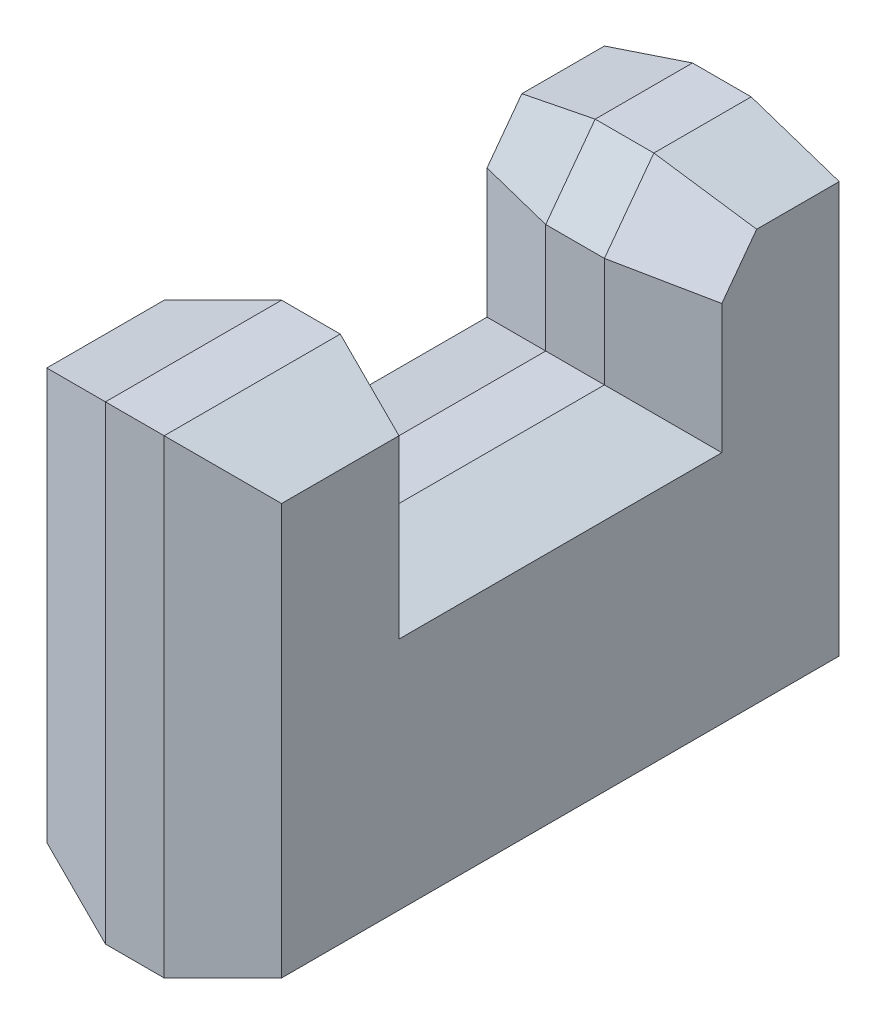
SolidWorks part; units mm, degrees
ref_plane "Front Plane" through (0, 0, 0) normal (0, 0, 1) x (1, 0, 0)
ref_plane "Top Plane" through (0, 0, 0) normal (0, 1, 0) x (1, 0, 0)
ref_plane "Right Plane" through (0, 0, 0) normal (1, 0, 0) x (0, 0, -1)
sketch "Sketch1" plane through (0, 0, 0) normal (0, 0, 1) x (1, 0, 0)
  line L0 (0, 4) -> (0, -4) construction
  line L1 (-2, 4) -> (2, 4)
  line L2 (-2, 4) -> (-2, -4)
  line L3 (-2, -4) -> (2, -4)
  line L4 (2, 4) -> (2, -4)
  line L5 (-2, 0) -> (2, 0) construction
  dimension "D1" = 4
  dimension "D2" = 8
extrude "Boss-Extrude1" add sketch "Sketch1" along normal blind 10
sketch "Sketch2" plane through (0, 0, 0) normal (1, 0, 0) x (0, 0, -1)
  line L0 (-2.5, 4) -> (-2.5, 1) construction
  line L1 (-2.5, 2.8666) -> (-1.6579, 4)
  line L2 (-2.5, 1) -> (-7, 1)
  line L3 (-7, 1) -> (-7, 4)
  line L5 (-7, 4) -> (-2.5, 4)
  line L6 (0, 4) -> (0, -4) construction
  line L7 (-1.6579, 4) -> (-2.5, 4)
  line L8 (-2.5, 2.8666) -> (-2.5, 1)
  dimension "D1" = 4.5
  dimension "D2" = 3
  dimension "D3" = 2.5
extrude "Cut-Extrude1" cut sketch "Sketch2" against normal through all both and the other way through all
chamfer "Chamfer4" distance 0.5 distance2 1.5 8 edges at (-2, -4, 5) (-2, 4, 0.829) (-2, 3.4333, 2.079) (-2, 1.9333, 2.5) (-2, 1, 4.75) (-2, 2.5, 7) (-2, 4, 8.5) (-2, 0, 10) first distance on face at (-2, 1.4296, 4.5175)
chamfer "Chamfer5" distance 1.5 distance2 0.5 8 edges at (2, 4, 0.829) (2, 3.4333, 2.079) (2, 1.9333, 2.5) (2, 1, 4.75) (2, 2.5, 7) (2, 4, 8.5) (2, 0, 10) (2, -4, 5) first distance on face at (0.75, 4, 0.829) first distance on face at (0.75, 3.4333, 2.079) first distance on face at (0.75, 1.9333, 2.5) first distance on face at (0.75, 1, 4.75) first distance on face at (0.75, 2.5, 7) first distance on face at (0.75, 4, 8.5) first distance on face at (0.75, 0, 10) first distance on face at (0.75, -4, 5)
